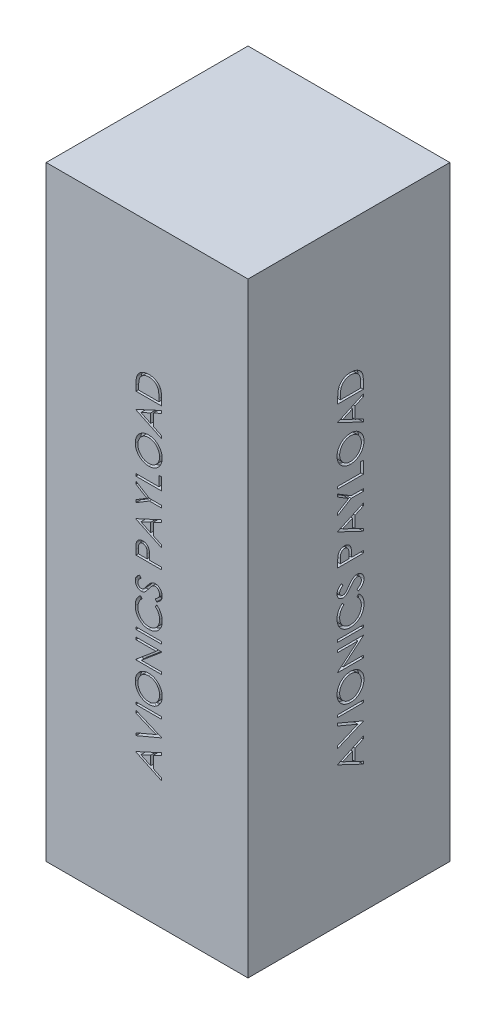
SolidWorks part; units mm, degrees
ref_plane "Front Plane" through (0, 0, 0) normal (0, 0, 1) x (1, 0, 0)
ref_plane "Top Plane" through (0, 0, 0) normal (0, 1, 0) x (1, 0, 0)
ref_plane "Right Plane" through (0, 0, 0) normal (1, 0, 0) x (0, 0, -1)
sketch "Sketch1" plane through (0, 0, 0) normal (0, 1, 0) x (1, 0, 0)
  line L1 (-50, -50) -> (50, -50)
  line L2 (-50, -50) -> (-50, 50)
  line L3 (-50, 50) -> (50, 50)
  line L4 (50, -50) -> (50, 50)
  line L5 (-50, -50) -> (50, 50) construction
  line L6 (-50, 50) -> (50, -50) construction
  point P0 (0, 0)
  dimension "D1" = 100
  dimension "D2" = 100
extrude "Boss-Extrude1" add sketch "Sketch1" along normal blind 300
sketch "Sketch6" plane through (-50, 0, 0) normal (-1, 0, 0) x (0, 0, 1)
  line L0 (7.15, 0) -> (7.15, 300) construction
  line L1 (-50, 0) -> (50, 0) construction
  line L2 (-50, 300) -> (50, 300) construction
  line L3 (-50, 300) -> (-50, 0) construction
  text T0 "AVIONICS PAYLOAD" font "Century Gothic" height in points 48
  dimension "D1" = 57.15
extrude "Cut-Extrude1" cut sketch "Sketch6" against normal blind 2.54
sketch "Sketch8" plane through (0, 0, -50) normal (0, 0, -1) x (-1, 0, 0)
  line L0 (7.15, 0) -> (7.15, 300) construction
  line L1 (-50, 0) -> (50, 0) construction
  line L2 (-50, 300) -> (50, 300) construction
  line L3 (-50, 300) -> (-50, 0) construction
  text T0 "AVIONICS PAYLOAD" font "Century Gothic" height in points 48
  dimension "D1" = 57.15
extrude "Cut-Extrude2" cut sketch "Sketch8" against normal blind 2.54
sketch "Sketch9" plane through (50, 0, 0) normal (1, 0, 0) x (0, 0, -1)
  line L0 (7.15, 0) -> (7.15, 300) construction
  line L1 (-50, 0) -> (50, 0) construction
  line L2 (-50, 300) -> (50, 300) construction
  line L3 (-50, 300) -> (-50, 0) construction
  text T0 "AVIONICS PAYLOAD" font "Century Gothic" height in points 48
  dimension "D1" = 57.15
extrude "Cut-Extrude3" cut sketch "Sketch9" against normal blind 2.54
sketch "Sketch11" plane through (0, 0, 50) normal (0, 0, 1) x (1, 0, 0)
  line L0 (7.15, 0) -> (7.15, 300) construction
  line L1 (-50, 0) -> (50, 0) construction
  line L2 (-50, 300) -> (50, 300) construction
  line L3 (-50, 300) -> (-50, 0) construction
  text T0 "AVIONICS PAYLOAD" font "Century Gothic" height in points 48
  dimension "D1" = 57.15
extrude "Cut-Extrude4" cut sketch "Sketch11" against normal blind 2.54
